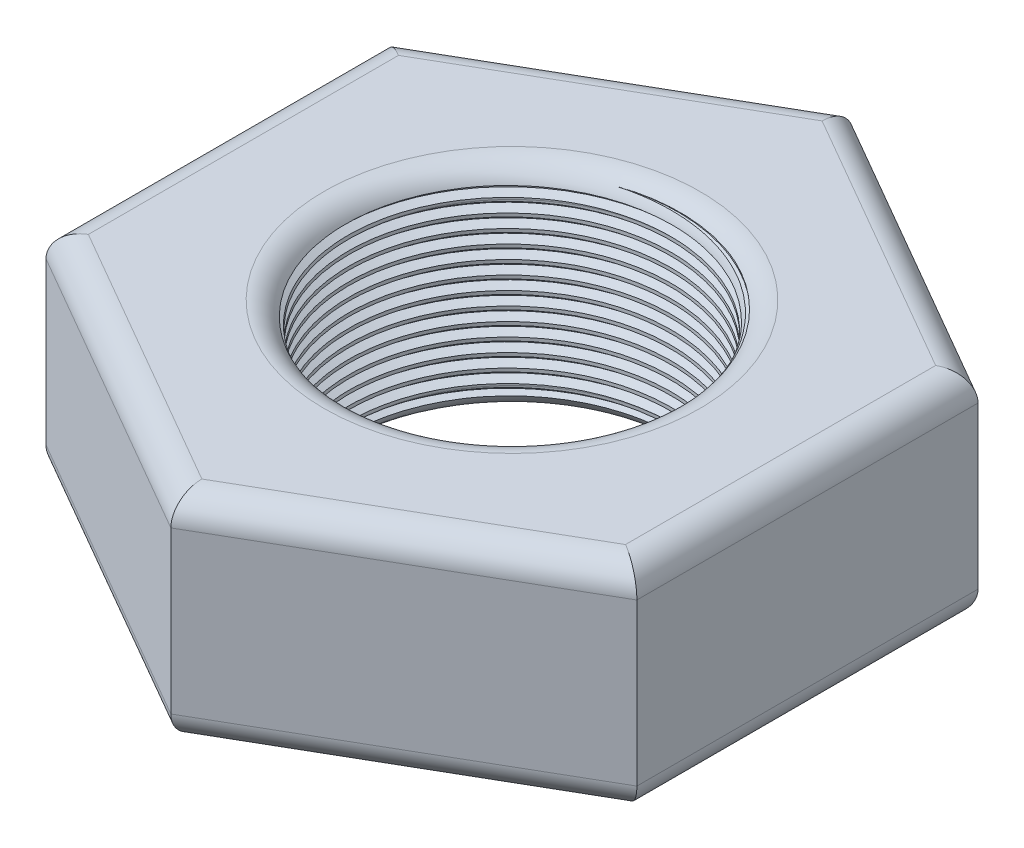
SolidWorks part; units mm, degrees
ref_plane "Front Plane" through (0, 0, 0) normal (0, 0, 1) x (1, 0, 0)
ref_plane "Top Plane" through (0, 0, 0) normal (0, 1, 0) x (1, 0, 0)
ref_plane "Right Plane" through (0, 0, 0) normal (1, 0, 0) x (0, 0, -1)
sketch "Sketch1" plane through (0, 0, 0) normal (0, 1, 0) x (1, 0, 0)
  line L0 (0, 0) -> (0, 6.3509) construction
  line L2 (0, 6.3509) -> (-5.5, 3.1754)
  line L3 (-5.5, 3.1754) -> (-5.5, -3.1754)
  line L4 (-5.5, -3.1754) -> (0, -6.3509)
  line L5 (0, -6.3509) -> (5.5, -3.1754)
  line L6 (5.5, -3.1754) -> (5.5, 3.1754)
  line L7 (5.5, 3.1754) -> (0, 6.3509)
  circle A0 centre (0, 0) radius 5.5 construction
  circle A1 centre (0, 0) radius 3
  dimension "D1" = 11
  dimension "D2" = 6
extrude "Boss-Extrude1" add sketch "Sketch1" along normal blind 4
fillet "Fillet1" radius 0.5 14 edges at (5.5, 4, 0) (2.75, 4, 4.7631) (-2.75, 4, 4.7631) (-5.5, 4, 0) (-2.75, 4, -4.7631) (2.75, 4, -4.7631) (0, 0, 3) (2.75, 0, 4.7631) (5.5, 0, 0) (2.75, 0, -4.7631) (-2.75, 0, -4.7631) (-5.5, 0, 0) (-2.75, 0, 4.7631) (0, 4, 3)
thread "Thread1" pitch 0.25 method cut profile "Thread Profile1" start angle 0, offset 1, length 10, pitch 0.25, diameter 6
ref_plane "Plane1" through (-3, 4.5, 0) normal (0, 0, 1) x (-1, 0, 0)
sketch "Thread Profile1" plane through (-3, 4.5, 0) normal (0, 0, 1) x (-1, 0, 0)
  line L0 (0, 0) -> (0, 0.25) construction
  line L1 (0, 0) -> (0.1353, 0.0781)
  line L2 (0.1353, 0.0781) -> (0.1353, 0.1094)
  line L3 (0.1353, 0.1094) -> (0, 0.1875)
  line L4 (0.1353, 0.0937) -> (0, 0.0937) construction
  line L11 (0, 0) -> (0, 0.1875)
  point P2 (0, 0)
  dimension "Pitch" = 0.25
  dimension "Profile_Angle" = 60
  dimension "Profile_Land" = 0.0312
  dimension "Profile_Height" = 0.1353
